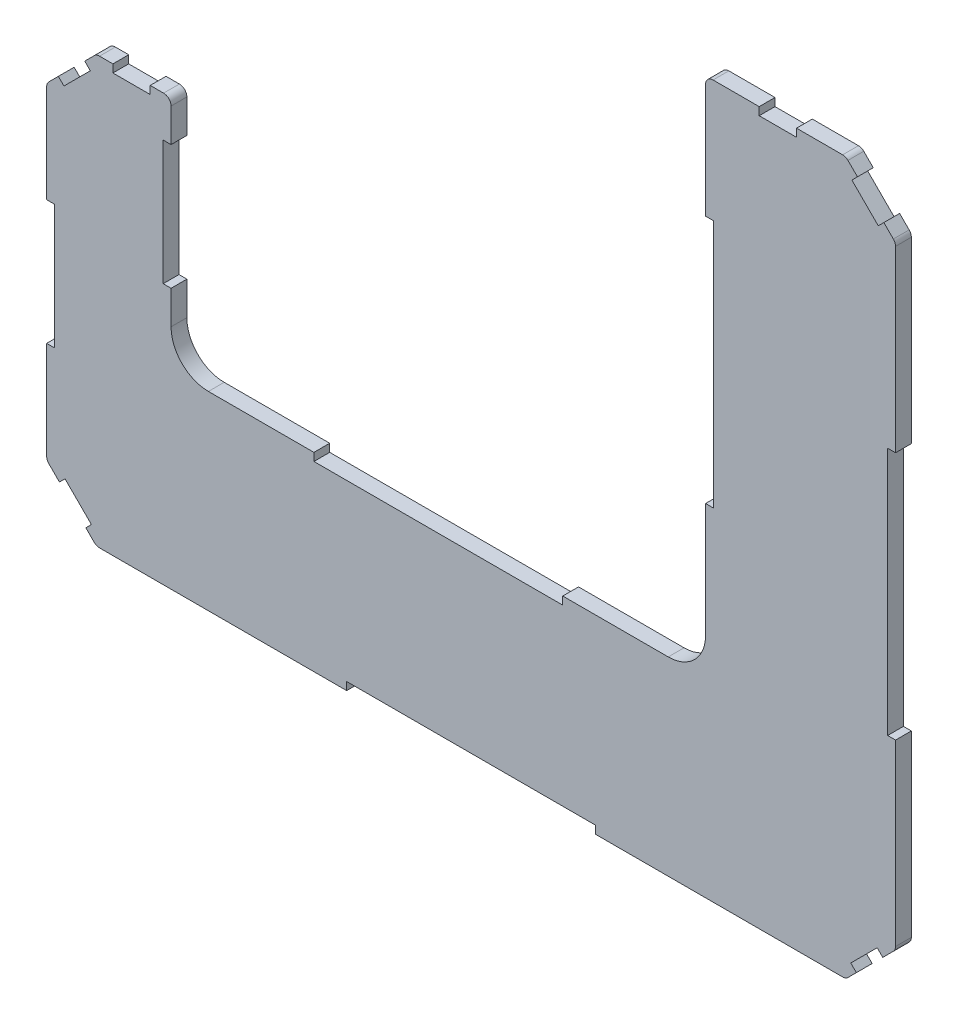
SolidWorks part; units mm, degrees
material "Teak"
ref_plane "Front Plane" through (0, 0, 0) normal (0, 0, 1) x (1, 0, 0)
ref_plane "Top Plane" through (0, 0, 0) normal (0, 1, 0) x (1, 0, 0)
ref_plane "Right Plane" through (0, 0, 0) normal (1, 0, 0) x (0, 0, -1)
sketch "Sketch2" plane through (0, 0, 0) normal (0, 0, 1) x (1, 0, 0)
  line L0 (-157.4125, 94.825) -> (-107.4125, 94.825)
  line L1 (-107.4125, 94.825) -> (-107.4125, 0)
  line L2 (-107.4125, 0) -> (107.4125, 0)
  line L3 (107.4125, 0) -> (107.4125, 209.825)
  line L4 (107.4125, 209.825) -> (183.7625, 209.825)
  line L5 (183.7625, 209.825) -> (183.7625, -76.35)
  line L6 (183.7625, -76.35) -> (58.275, -76.35)
  line L7 (-31.925, -76.35) -> (58.275, -76.35)
  line L10 (-31.925, -76.35) -> (-157.4125, -76.35)
  line L11 (-157.4125, -76.35) -> (-157.4125, 94.825)
  line L12 (-37.4125, 0) -> (-37.4125, 144.825) construction
  point P10 (-37.4125, 0)
  point P14 (107.4125, 144.825)
  point P15 (-37.4125, 94.825)
  dimension "D1" = 144.825
  dimension "D2" = 144.825
  dimension "D6" = 90.2
  dimension "D7" = 76.35
  dimension "D10" = 50
  dimension "D11" = 50
extrude "Boss-Extrude1" add sketch "Sketch2" along normal blind 3.175 and the other way blind 3.175
chamfer "Chamfer1" distance 20 angle 45 4 edges at (-157.4125, -76.35, 0) (183.7625, -76.35, 0) (183.7625, 209.825, 0) (-157.4125, 94.825, 0)
fillet "Fillet1" radius 15 2 edges at (107.4125, 0, 0) (-107.4125, 0, 0)
fillet "Fillet2" radius 3 8 edges at (183.7625, -56.35, 0) (-157.4125, -56.35, 0) (-157.4125, 74.825, 0) (-137.4125, 94.825, 0) (-107.4125, 94.825, 0) (183.7625, 189.825, 0) (163.7625, 209.825, 0) (107.4125, 209.825, 0)
sketch "Sketch3" plane through (0, 0, 3.175) normal (0, 0, 1) x (1, 0, 0)
  line L0 (-94.6381, 69.9757) -> (-94.6381, 14.7992)
  line L1 (-94.6381, 14.7992) -> (-97.8131, 14.7992)
  line L2 (-97.8131, 14.7992) -> (-97.8131, 69.9757)
  line L3 (-97.8131, 69.9757) -> (-94.6381, 69.9757)
  line L4 (-127.4635, 65.4691) -> (-114.3536, 78.579)
  line L5 (-114.3536, 78.579) -> (-112.1085, 76.3339)
  line L6 (-112.1085, 76.3339) -> (-125.2184, 63.2241)
  line L7 (-125.2184, 63.2241) -> (-127.4635, 65.4691)
  line L8 (-129.3392, 54.7846) -> (-126.1642, 54.7846)
  line L9 (-126.1642, 54.7846) -> (-126.1642, -28.3138)
  line L10 (-126.1642, -28.3138) -> (-129.3392, -28.3138)
  line L11 (-129.3392, -28.3138) -> (-129.3392, 54.7846)
  line L12 (-127.4635, -37.1329) -> (-125.2184, -34.8879)
  line L13 (-125.2184, -34.8879) -> (-110.9382, -49.1681)
  line L14 (-110.9382, -49.1681) -> (-113.1832, -51.4132)
  line L15 (-113.1832, -51.4132) -> (-127.4635, -37.1329)
  line L16 (-67.7784, -44.3183) -> (-67.7784, -41.1433)
  line L17 (-67.7784, -41.1433) -> (53.0181, -41.1433)
  line L18 (53.0181, -41.1433) -> (53.0181, -44.3183)
  line L19 (53.0181, -44.3183) -> (-67.7784, -44.3183)
  line L20 (114.9313, -49.5303) -> (117.1763, -51.7753)
  line L21 (117.1763, -51.7753) -> (131.7883, -37.1634)
  line L22 (131.7883, -37.1634) -> (129.5432, -34.9183)
  line L23 (129.5432, -34.9183) -> (114.9313, -49.5303)
  line L24 (-67.7784, -4.1746) -> (-67.7784, -7.3496)
  line L25 (-67.7784, -7.3496) -> (63.5847, -7.3496)
  line L26 (63.5847, -7.3496) -> (63.5847, -4.1746)
  line L27 (63.5847, -4.1746) -> (-67.7784, -4.1746)
  line L28 (92.7516, 20.9162) -> (91.2159, 151.9937)
  line L29 (91.2159, 151.9937) -> (94.3909, 151.9937)
  line L30 (94.3909, 151.9937) -> (95.9266, 20.9162)
  line L31 (95.9266, 20.9162) -> (92.7516, 20.9162)
  line L32 (96.8341, 161.8762) -> (96.8341, 158.7012)
  line L33 (96.8341, 158.7012) -> (112.5649, 158.7012)
  line L34 (112.5649, 158.7012) -> (112.5649, 161.8762)
  line L35 (112.5649, 161.8762) -> (96.8341, 161.8762)
  line L37 (117.7781, 156.4535) -> (120.0231, 158.6985)
  line L38 (120.0231, 158.6985) -> (133.8694, 144.8523)
  line L39 (133.8694, 144.8523) -> (131.6243, 142.6072)
  line L40 (131.6243, 142.6072) -> (117.7781, 156.4535)
  line L41 (129.9213, 134.1701) -> (133.0963, 134.1701)
  line L42 (133.0963, 134.1701) -> (133.0963, -24.961)
  line L43 (133.0963, -24.961) -> (129.9213, -24.961)
  line L44 (129.9213, -24.961) -> (129.9213, 134.1701)
  line L45 (163.7625, -76.35) -> (182.8838, -57.2287) construction
  line L46 (-156.5338, -57.2287) -> (-137.4125, -76.35) construction
  line L47 (-138.2912, 93.9463) -> (-156.5338, 75.7037) construction
  line L48 (182.8838, 190.7037) -> (164.6412, 208.9463) construction
  dimension "D1" = 3.175
extrude "Cut-Extrude1" [suppressed] cut sketch "Sketch3" against normal through all
sketch "magnets" plane through (0, 0, 3.175) normal (0, 0, 1) x (1, 0, 0)
  point P0 (94.6751, 158.4052)
  point P1 (114.7572, -50)
  point P2 (131.9288, 140.6094)
  point P3 (131.9288, -32.8111)
  point P4 (0, -44.1618)
  point P5 (-114.0039, -50)
  point P6 (-130.8821, -32.8111)
  point P9 (-130.8821, 62.3605)
  point P10 (-93.5499, 79.7316)
  point P12 (0, -4.7392)
sketch "Sketch4" plane through (0, 0, 3.175) normal (0, 0, 1) x (1, 0, 0)
  line L0 (128.9662, 209.825) -> (128.9662, 206.65)
  line L1 (162.5199, 209.825) -> (110.4125, 209.825) construction
  line L2 (128.9662, 206.65) -> (143.9662, 206.65)
  line L3 (143.9662, 206.65) -> (143.9662, 209.825)
  line L4 (168.4592, 205.1283) -> (166.2141, 202.8832)
  line L5 (-138.2912, 93.9463) -> (-156.5338, 75.7037) construction
  line L6 (166.2141, 202.8832) -> (176.8207, 192.2766)
  line L7 (176.8207, 192.2766) -> (179.0658, 194.5217)
  line L8 (-107.4125, 15) -> (-107.4125, 91.825) construction
  line L9 (-107.4125, 78.4125) -> (-110.5875, 78.4125)
  line L11 (-107.4125, 78.4125) -> (-107.4125, 28.4125)
  line L12 (-107.4125, 28.4125) -> (-110.5875, 28.4125)
  line L13 (-110.5875, 78.4125) -> (-110.5875, 28.4125)
  line L15 (-157.4125, 73.5824) -> (-157.4125, -55.1074) construction
  line L16 (-157.4125, 34.2375) -> (-154.2375, 34.2375)
  line L17 (-137.4125, -76.35) -> (163.7625, -76.35) construction
  line L19 (-157.4125, 34.2375) -> (-157.4125, -15.7625)
  line L20 (-157.4125, -15.7625) -> (-154.2375, -15.7625)
  line L21 (-154.2375, 34.2375) -> (-154.2375, -15.7625)
  line L23 (-152.2765, -61.486) -> (-141.6699, -72.0926)
  line L24 (-156.5338, -57.2287) -> (-137.4125, -76.35) construction
  line L25 (-141.6699, -72.0926) -> (-139.4248, -69.8476)
  line L26 (-139.4248, -69.8476) -> (-150.0314, -59.241)
  line L27 (-150.0314, -59.241) -> (-152.2765, -61.486)
  line L28 (-152.7158, 79.5217) -> (-150.4707, 77.2766)
  line L29 (-144.7281, -64.5443) -> (-146.9732, -66.7893) construction
  line L30 (-150.4707, 77.2766) -> (-139.8641, 87.8832)
  line L31 (-139.8641, 87.8832) -> (-142.1092, 90.1283)
  line L32 (-130.7912, 94.825) -> (-130.7912, 91.65)
  line L33 (-36.825, -76.35) -> (63.175, -76.35)
  line L35 (-130.7912, 91.65) -> (-115.7912, 91.65)
  line L36 (-36.825, -76.35) -> (-36.825, -73.175)
  line L37 (183.7625, -55.1074) -> (183.7625, 188.5824) construction
  line L39 (-36.825, -73.175) -> (63.175, -73.175)
  line L40 (63.175, -76.35) -> (63.175, -73.175)
  line L41 (-50, -3.175) -> (50, -3.175)
  line L42 (-50, -3.175) -> (-50, 0)
  line L43 (-50, 0) -> (50, 0)
  line L44 (50, -3.175) -> (50, 0)
  line L45 (92.4125, 0) -> (-92.4125, 0) construction
  line L46 (107.4125, 206.825) -> (107.4125, 15) construction
  line L47 (107.4125, 160.9125) -> (110.5875, 160.9125)
  line L48 (107.4125, 160.9125) -> (107.4125, 60.9125)
  line L49 (107.4125, 60.9125) -> (110.5875, 60.9125)
  line L50 (110.5875, 160.9125) -> (110.5875, 60.9125)
  line L51 (182.8838, 190.7037) -> (164.6412, 208.9463) construction
  line L52 (183.7625, 116.7375) -> (180.5875, 116.7375)
  line L53 (183.7625, 116.7375) -> (183.7625, 16.7375)
  line L55 (183.7625, 16.7375) -> (180.5875, 16.7375)
  line L56 (180.5875, 116.7375) -> (180.5875, 16.7375)
  line L57 (168.0199, -72.0926) -> (165.7748, -69.8476)
  line L58 (163.7625, -76.35) -> (182.8838, -57.2287) construction
  line L59 (-147.4125, 84.825) -> (-145.1674, 82.5799) construction
  line L60 (-123.2912, 91.65) -> (-123.2912, 94.825) construction
  line L61 (171.5174, 197.5799) -> (173.7625, 199.825) construction
  line L62 (165.7748, -69.8476) -> (176.3814, -59.241)
  line L63 (176.3814, -59.241) -> (178.6265, -61.486)
  line L64 (171.0781, -64.5443) -> (173.3232, -66.7893)
  line L71 (-115.7912, 91.65) -> (-115.7912, 94.825)
  line L77 (-110.4125, 94.825) -> (-136.1699, 94.825) construction
  point P20 (-110.5875, 53.4125)
  point P21 (-107.4125, 53.4125)
  point P28 (-154.2375, 9.2375)
  point P29 (-157.4125, 9.2375)
  point P36 (-144.7281, -64.5443)
  point P51 (13.175, -76.35)
  point P58 (0, -3.175)
  point P67 (107.4125, 110.9125)
  point P76 (183.7625, 66.7375)
  point P106 (136.4662, 206.65)
  point P107 (136.4662, 209.825)
  point P109 (171.5174, 197.5799)
  line M1 (163.7625, -76.35) -> (182.8838, -57.2287)
  line M3 (183.7625, -55.1074) -> (183.7625, 188.5824)
  line M5 (182.8838, 190.7037) -> (164.6412, 208.9463)
  line M7 (162.5199, 209.825) -> (110.4125, 209.825)
  line M9 (107.4125, 206.825) -> (107.4125, 15)
  line M11 (92.4125, 0) -> (-92.4125, 0)
  line M13 (-107.4125, 15) -> (-107.4125, 91.825)
  line M15 (-110.4125, 94.825) -> (-136.1699, 94.825)
  line M17 (-138.2912, 93.9463) -> (-156.5338, 75.7037)
  line M19 (-157.4125, 73.5824) -> (-157.4125, -55.1074)
  line M21 (-156.5338, -57.2287) -> (-137.4125, -76.35)
  line M28 (-137.4125, -76.35) -> (163.7625, -76.35)
  dimension "D1" = 3.175
  dimension "D2" = 15
  dimension "D3" = 50
  dimension "D4" = 15
  dimension "D5" = 100
extrude "wall_slots" cut sketch "Sketch4" against normal blind 60 contours L9 L13 L12 M13 | L35 L71 L32 M15 | L30 L31 L28 M17 | L21 L16 L20 M19 | L26 L27 L25 M21 | L40 L39 L36 M28 | L41 L44 L42 M11 | L64 L62 L57 M1 | L62 L64 L63 M1 | L52 L56 L55 M3 | L50 L47 L49 M9 | L2 L3 L0 M7 | L6 L7 L4 M5 region at (136.4662, 208.2375, 3.175) region at (172.64, 198.7025, 3.175) region at (-109, 53.4125, 3.175) region at (-155.825, 9.2375, 3.175) region at (-145.8506, -65.6668, 3.175) region at (169.549, -68.3185, 3.175) region at (13.175, -74.7625, 3.175) region at (174.8523, -63.0152, 3.175) region at (-146.29, 83.7025, 3.175) region at (-123.2912, 93.2375, 3.175) region at (0, -1.5875, 3.175) region at (109, 110.9125, 3.175) region at (182.175, 66.7375, 3.175)
fillet "Fillet3" radius 3 2 edges at (163.7625, -76.35, 0) (-137.4125, -76.35, 0)
sketch "wall_measure" plane through (0, 0, 3.175) normal (0, 0, 1) x (1, 0, 0)
  line L0 (-136.1699, 94.825) -> (-136.1699, 91.65)
  line L1 (-136.1699, 91.65) -> (-110.4125, 91.65)
  line L2 (-110.4125, 91.65) -> (-110.4125, 94.825)
  line L3 (-110.5875, 78.4125) -> (-110.5875, 28.4125) construction
  line L4 (110.4125, 209.825) -> (110.4125, 206.65)
  line L5 (110.4125, 206.65) -> (162.5199, 206.65)
  line L6 (162.5199, 206.65) -> (162.5199, 209.825)
  line L7 (128.9662, 206.65) -> (143.9662, 206.65) construction
  line L8 (164.6412, 208.9463) -> (162.3961, 206.7013)
  line L9 (162.3961, 206.7013) -> (180.6388, 188.4586)
  line L10 (180.6388, 188.4586) -> (182.8838, 190.7037)
  line L11 (182.8838, 190.7037) -> (179.0658, 194.5217) construction
  line L12 (107.4125, 206.825) -> (110.5875, 206.825)
  line L13 (110.5875, 206.825) -> (110.5875, 15)
  line L14 (110.5875, 15) -> (107.4125, 15)
  line L15 (107.4125, 60.9125) -> (107.4125, 15) construction
  line L16 (183.7625, 188.5824) -> (180.5875, 188.5824)
  line L17 (180.5875, 188.5824) -> (180.5875, -55.1074)
  line L18 (180.5875, -55.1074) -> (183.7625, -55.1074)
  line L19 (-92.4125, 0) -> (-92.4125, -3.175)
  line L20 (-92.4125, -3.175) -> (92.4125, -3.175)
  line L21 (92.4125, -3.175) -> (92.4125, 0)
  line L22 (-36.825, -73.175) -> (63.175, -73.175) construction
  line L23 (162.5199, -76.35) -> (-136.1699, -76.35)
  line L24 (162.5199, -76.35) -> (162.5199, -73.175)
  line L25 (162.5199, -73.175) -> (-136.1699, -73.175)
  line L26 (-136.1699, -76.35) -> (-136.1699, -73.175)
  line L27 (182.8838, -57.2287) -> (180.6388, -54.9836)
  line L28 (180.6388, -54.9836) -> (162.3961, -73.2263)
  line L29 (162.3961, -73.2263) -> (164.6412, -75.4713)
  line L32 (-50, -3.175) -> (50, -3.175) construction
  line L33 (180.5875, 116.7375) -> (180.5875, 16.7375) construction
  line L34 (-157.4125, 73.5824) -> (-154.4125, 73.5824)
  line L35 (-154.4125, 73.5824) -> (-154.4125, -55.1074)
  line L36 (-154.4125, -55.1074) -> (-157.4125, -55.1074)
  line L37 (-107.4125, 91.825) -> (-110.5875, 91.825)
  line L38 (-110.5875, 91.825) -> (-110.5875, 15)
  line L39 (-110.5875, 15) -> (-107.4125, 15)
  line L44 (166.2141, 202.8832) -> (176.8207, 192.2766) construction
  line L46 (165.7748, -69.8476) -> (176.3814, -59.241) construction
  line L47 (-130.7912, 91.65) -> (-115.7912, 91.65) construction
  line L48 (110.5875, 160.9125) -> (110.5875, 60.9125) construction
  line L49 (-156.5338, -57.2287) -> (-154.2888, -54.9836)
  line L50 (-154.2888, -54.9836) -> (-136.0461, -73.2263)
  line L51 (-136.0461, -73.2263) -> (-138.2912, -75.4713)
  line L52 (-141.6699, -72.0926) -> (-138.2912, -75.4713) construction
  line L53 (-139.4248, -69.8476) -> (-150.0314, -59.241) construction
  arc A0 (92.4125, 0) -> (107.4125, 15) centre (92.4125, 15) ccw construction
  arc A1 (-107.4125, 15) -> (-92.4125, 0) centre (-92.4125, 15) ccw construction
  point P98 (-156.5338, -57.2287)
  point P99 (-138.2912, -75.4713)
  dimension "D1" = 25.7574
  dimension "D2" = 52.1074
  dimension "D3" = 25.799
  dimension "D4" = 191.825
  dimension "D5" = 243.6897
  dimension "D6" = 184.825
  dimension "D7" = 298.6897
  dimension "D8" = 25.799
  dimension "D11" = 128.6897
  dimension "D12" = 76.825
  dimension "D13" = 25.799
sketch "Sketch5" plane through (0, 0, 3.175) normal (0, 0, 1) x (1, 0, 0)
  line L60 (176.8207, 192.2766) -> (166.2141, 202.8832)
  line L61 (176.8207, 192.2766) -> (166.2141, 202.8832)
  line L62 (166.2141, 202.8832) -> (168.4592, 205.1283)
  line L63 (166.2141, 202.8832) -> (168.4592, 205.1283)
  line L64 (143.9662, 209.825) -> (143.9662, 206.65)
  line L65 (143.9662, 209.825) -> (143.9662, 206.65)
  line L66 (143.9662, 206.65) -> (128.9662, 206.65)
  line L67 (143.9662, 206.65) -> (128.9662, 206.65)
  line L68 (128.9662, 206.65) -> (128.9662, 209.825)
  line L69 (128.9662, 206.65) -> (128.9662, 209.825)
  line L70 (128.9662, 209.825) -> (110.4125, 209.825)
  line L71 (128.9662, 209.825) -> (110.4125, 209.825)
  line L72 (-107.4125, 28.4125) -> (-110.5875, 28.4125)
  line L73 (-107.4125, 28.4125) -> (-110.5875, 28.4125)
  line L74 (168.4592, 205.1283) -> (164.6412, 208.9463)
  line L75 (162.5199, 209.825) -> (143.9662, 209.825)
  line L76 (107.4125, 60.9125) -> (107.4125, 15)
  line L77 (107.4125, 60.9125) -> (107.4125, 15)
  line L78 (-157.4125, 34.2375) -> (-154.2375, 34.2375)
  line L79 (-157.4125, 34.2375) -> (-154.2375, 34.2375)
  line L80 (107.4125, 206.825) -> (107.4125, 160.9125)
  line L81 (-50, 0) -> (-92.4125, 0)
  line L82 (-50, 0) -> (-92.4125, 0)
  line L83 (-107.4125, 78.4125) -> (-107.4125, 91.825)
  line L84 (-107.4125, 78.4125) -> (-107.4125, 91.825)
  line L85 (92.4125, 0) -> (50, 0)
  line L86 (-115.7912, 94.825) -> (-115.7912, 91.65)
  line L87 (-115.7912, 94.825) -> (-115.7912, 91.65)
  line L88 (-115.7912, 91.65) -> (-130.7912, 91.65)
  line L89 (-115.7912, 91.65) -> (-130.7912, 91.65)
  line L90 (-107.4125, 15) -> (-107.4125, 28.4125)
  line L91 (-130.7912, 91.65) -> (-130.7912, 94.825)
  line L92 (-130.7912, 91.65) -> (-130.7912, 94.825)
  line L93 (-130.7912, 94.825) -> (-136.1699, 94.825)
  line L94 (-130.7912, 94.825) -> (-136.1699, 94.825)
  line L95 (-110.4125, 94.825) -> (-115.7912, 94.825)
  line L96 (-142.1092, 90.1283) -> (-139.8641, 87.8832)
  line L97 (-142.1092, 90.1283) -> (-139.8641, 87.8832)
  line L98 (-139.8641, 87.8832) -> (-150.4707, 77.2766)
  line L99 (-139.8641, 87.8832) -> (-150.4707, 77.2766)
  line L100 (-138.2912, 93.9463) -> (-142.1092, 90.1283)
  line L101 (-150.4707, 77.2766) -> (-152.7158, 79.5217)
  line L102 (-150.4707, 77.2766) -> (-152.7158, 79.5217)
  line L103 (-152.7158, 79.5217) -> (-156.5338, 75.7037)
  line L104 (-152.7158, 79.5217) -> (-156.5338, 75.7037)
  line L105 (-157.4125, 73.5824) -> (-157.4125, 34.2375)
  line L106 (-36.825, -73.175) -> (63.175, -73.175)
  line L107 (-36.825, -73.175) -> (63.175, -73.175)
  line L108 (-157.4125, -15.7625) -> (-157.4125, -55.1074)
  line L109 (-157.4125, -15.7625) -> (-157.4125, -55.1074)
  line L110 (-156.5338, -57.2287) -> (-152.2765, -61.486)
  line L111 (180.5875, 116.7375) -> (183.7625, 116.7375)
  line L112 (180.5875, 116.7375) -> (183.7625, 116.7375)
  line L113 (63.175, -76.35) -> (162.5199, -76.35)
  line L114 (63.175, -76.35) -> (162.5199, -76.35)
  line L115 (164.6412, -75.4713) -> (168.0199, -72.0926)
  line L116 (107.4125, 160.9125) -> (110.5875, 160.9125)
  line L117 (107.4125, 160.9125) -> (110.5875, 160.9125)
  line L118 (-139.4248, -69.8476) -> (-141.6699, -72.0926)
  line L119 (-139.4248, -69.8476) -> (-141.6699, -72.0926)
  line L120 (183.7625, 16.7375) -> (180.5875, 16.7375)
  line L121 (183.7625, 16.7375) -> (180.5875, 16.7375)
  line L122 (164.6412, -75.4713) -> (168.0199, -72.0926)
  line L123 (-141.6699, -72.0926) -> (-138.2912, -75.4713)
  line L124 (178.6265, -61.486) -> (182.8838, -57.2287)
  line L125 (178.6265, -61.486) -> (182.8838, -57.2287)
  line L126 (-154.2375, -15.7625) -> (-157.4125, -15.7625)
  line L127 (-154.2375, -15.7625) -> (-157.4125, -15.7625)
  line L128 (183.7625, 116.7375) -> (183.7625, 188.5824)
  line L129 (183.7625, 116.7375) -> (183.7625, 188.5824)
  line L130 (182.8838, 190.7037) -> (179.0658, 194.5217)
  line L131 (182.8838, 190.7037) -> (179.0658, 194.5217)
  line L132 (-141.6699, -72.0926) -> (-138.2912, -75.4713)
  line L133 (179.0658, 194.5217) -> (176.8207, 192.2766)
  line L134 (179.0658, 194.5217) -> (176.8207, 192.2766)
  line L135 (110.5875, 160.9125) -> (110.5875, 60.9125)
  line L136 (110.5875, 160.9125) -> (110.5875, 60.9125)
  line L137 (183.7625, -55.1074) -> (183.7625, 16.7375)
  line L138 (110.5875, 60.9125) -> (107.4125, 60.9125)
  line L139 (110.5875, 60.9125) -> (107.4125, 60.9125)
  line L140 (50, 0) -> (50, -3.175)
  line L141 (50, 0) -> (50, -3.175)
  line L142 (50, -3.175) -> (-50, -3.175)
  line L143 (50, -3.175) -> (-50, -3.175)
  line L144 (-50, -3.175) -> (-50, 0)
  line L145 (-50, -3.175) -> (-50, 0)
  line L146 (168.4592, 205.1283) -> (164.6412, 208.9463)
  line L147 (162.5199, 209.825) -> (143.9662, 209.825)
  line L148 (-110.5875, 28.4125) -> (-110.5875, 78.4125)
  line L149 (-110.5875, 28.4125) -> (-110.5875, 78.4125)
  line L150 (-110.5875, 78.4125) -> (-107.4125, 78.4125)
  line L151 (-110.5875, 78.4125) -> (-107.4125, 78.4125)
  line L152 (107.4125, 206.825) -> (107.4125, 160.9125)
  line L153 (-154.2375, 34.2375) -> (-154.2375, -15.7625)
  line L154 (-154.2375, 34.2375) -> (-154.2375, -15.7625)
  line L155 (-152.2765, -61.486) -> (-150.0314, -59.241)
  line L156 (-152.2765, -61.486) -> (-150.0314, -59.241)
  line L157 (92.4125, 0) -> (50, 0)
  line L158 (-150.0314, -59.241) -> (-139.4248, -69.8476)
  line L159 (-150.0314, -59.241) -> (-139.4248, -69.8476)
  line L160 (-36.825, -76.35) -> (-36.825, -73.175)
  line L161 (-36.825, -76.35) -> (-36.825, -73.175)
  line L162 (-107.4125, 15) -> (-107.4125, 28.4125)
  line L163 (63.175, -73.175) -> (63.175, -76.35)
  line L164 (63.175, -73.175) -> (63.175, -76.35)
  line L165 (168.0199, -72.0926) -> (165.7748, -69.8476)
  line L166 (168.0199, -72.0926) -> (165.7748, -69.8476)
  line L167 (-110.4125, 94.825) -> (-115.7912, 94.825)
  line L168 (165.7748, -69.8476) -> (176.3814, -59.241)
  line L169 (165.7748, -69.8476) -> (176.3814, -59.241)
  line L170 (176.3814, -59.241) -> (178.6265, -61.486)
  line L171 (176.3814, -59.241) -> (178.6265, -61.486)
  line L172 (-138.2912, 93.9463) -> (-142.1092, 90.1283)
  line L173 (180.5875, 16.7375) -> (180.5875, 116.7375)
  line L174 (180.5875, 16.7375) -> (180.5875, 116.7375)
  line L175 (-136.1699, -76.35) -> (-36.825, -76.35)
  line L176 (-136.1699, -76.35) -> (-36.825, -76.35)
  line L177 (-157.4125, 73.5824) -> (-157.4125, 34.2375)
  line L182 (-156.5338, -57.2287) -> (-152.2765, -61.486)
  line L209 (183.7625, -55.1074) -> (183.7625, 16.7375)
  arc A10 (164.6412, 208.9463) -> (162.5199, 209.825) centre (162.5199, 206.825) ccw
  arc A11 (164.6412, 208.9463) -> (162.5199, 209.825) centre (162.5199, 206.825) ccw
  arc A12 (110.4125, 209.825) -> (107.4125, 206.825) centre (110.4125, 206.825) ccw
  arc A13 (110.4125, 209.825) -> (107.4125, 206.825) centre (110.4125, 206.825) ccw
  arc A14 (92.4125, 0) -> (107.4125, 15) centre (92.4125, 15) ccw
  arc A15 (-107.4125, 15) -> (-92.4125, 0) centre (-92.4125, 15) ccw
  arc A16 (-107.4125, 91.825) -> (-110.4125, 94.825) centre (-110.4125, 91.825) ccw
  arc A17 (-107.4125, 91.825) -> (-110.4125, 94.825) centre (-110.4125, 91.825) ccw
  arc A18 (-136.1699, 94.825) -> (-138.2912, 93.9463) centre (-136.1699, 91.825) ccw
  arc A19 (-136.1699, 94.825) -> (-138.2912, 93.9463) centre (-136.1699, 91.825) ccw
  arc A20 (-156.5338, 75.7037) -> (-157.4125, 73.5824) centre (-154.4125, 73.5824) ccw
  arc A21 (-156.5338, 75.7037) -> (-157.4125, 73.5824) centre (-154.4125, 73.5824) ccw
  arc A22 (-157.4125, -55.1074) -> (-156.5338, -57.2287) centre (-154.4125, -55.1074) ccw
  arc A23 (-157.4125, -55.1074) -> (-156.5338, -57.2287) centre (-154.4125, -55.1074) ccw
  arc A24 (182.8838, -57.2287) -> (183.7625, -55.1074) centre (180.7625, -55.1074) ccw
  arc A25 (182.8838, -57.2287) -> (183.7625, -55.1074) centre (180.7625, -55.1074) ccw
  arc A26 (92.4125, 0) -> (107.4125, 15) centre (92.4125, 15) ccw
  arc A27 (-107.4125, 15) -> (-92.4125, 0) centre (-92.4125, 15) ccw
  arc A28 (183.7625, 188.5824) -> (182.8838, 190.7037) centre (180.7625, 188.5824) ccw
  arc A29 (183.7625, 188.5824) -> (182.8838, 190.7037) centre (180.7625, 188.5824) ccw
  arc A32 (162.5199, -76.35) -> (164.6412, -75.4713) centre (162.5199, -73.35) ccw
  arc A33 (162.5199, -76.35) -> (164.6412, -75.4713) centre (162.5199, -73.35) ccw
  arc A34 (-138.2912, -75.4713) -> (-136.1699, -76.35) centre (-136.1699, -73.35) ccw
  arc A35 (-138.2912, -75.4713) -> (-136.1699, -76.35) centre (-136.1699, -73.35) ccw
  dimension "D1" = 0
equation "\"dX\"= 148mm - \"t_wood\" / 2"
equation "\"dY\"= 148mm - \"t_wood\" / 2"
equation "\"hmotor\"= 70mm"
equation "\"D1@Sketch2\"=\"dY\""
equation "\"D2@Sketch2\"=\"dX\""
equation "\"D5@Sketch2\"=\"hmotor\"+\"t_wood\""
equation "\"D6@Sketch2\"=\"hmotor\"+\"d_floor\"+\"t_wood\"*2"
equation "\"t_wood\"= 0.25in"
equation "\"D1@Boss-Extrude1\"=\"t_wood\"/2"
equation "\"D2@Boss-Extrude1\"=\"t_wood\"/2"
equation "\"D1@Sketch3\"=\"t_wood\"/2"
equation "\"d_floor\"= 7.50mm"
equation "\"D7@Sketch2\"=\"hmotor\" + \"t_wood\""
equation "\"D1@Sketch4\"=\"t_wood\" / 2"
